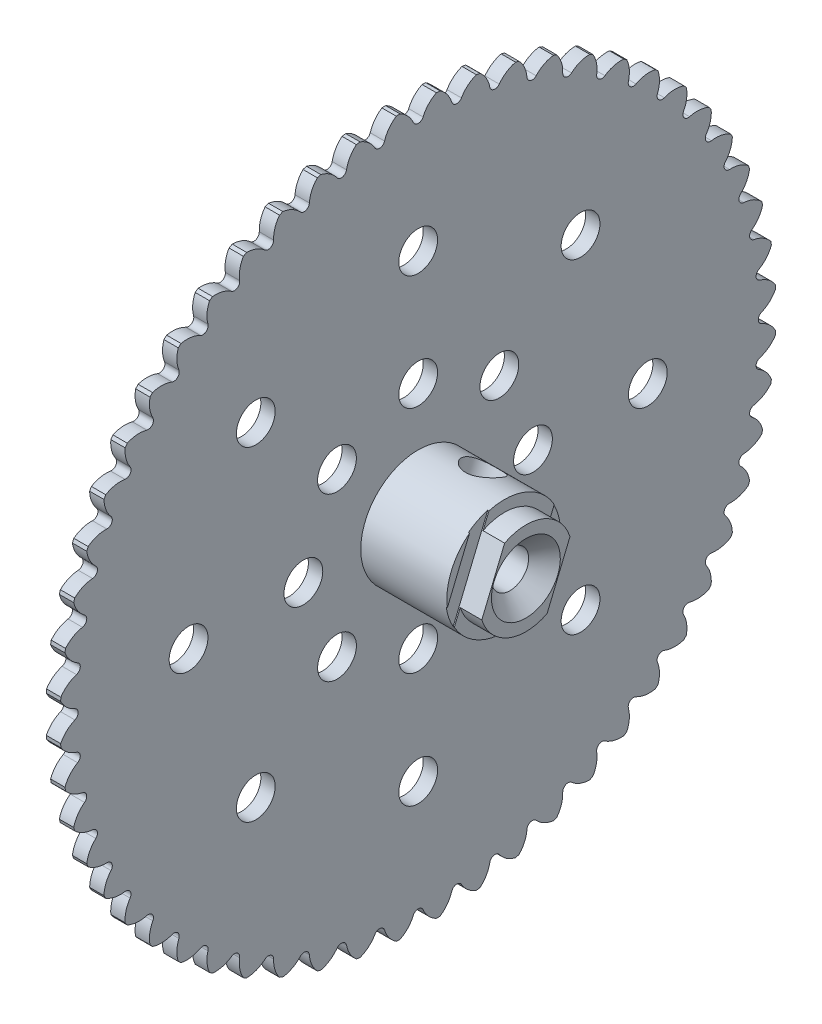
SolidWorks part; units mm, degrees
ref_plane "Front Plane" through (0, 0, 0) normal (0, 0, 1) x (1, 0, 0)
ref_plane "Top Plane" through (0, 0, 0) normal (0, 1, 0) x (1, 0, 0)
ref_plane "Right Plane" through (0, 0, 0) normal (1, 0, 0) x (0, 0, -1)
sketch "Sketch1" plane through (0, 0, 0) normal (1, 0, 0) x (0, 0, -1)
  circle A0 centre (0, 0) radius 39.5986
  dimension "D1" = 79.1972
extrude "Boss-Extrude1" add sketch "Sketch1" along normal blind 1.5875
sketch "Sketch2" plane through (1.5875, 0, 0) normal (1, 0, 0) x (0, 0, -1)
  circle A0 centre (0, 0) radius 12.7 construction
  circle A1 centre (0, 12.7) radius 2.1463
  circle A2 centre (0, 25.4) radius 2.1463
  circle A3 centre (0, 0) radius 25.4 construction
  dimension "D1" = 25.4
  dimension "D2" = 4.2926
  dimension "D3" = 50.8
extrude "Cut-Extrude1" cut sketch "Sketch2" against normal blind 1.5875
pattern_circular "CirPattern1" count 8 over 360 about axis through (1.5875, 0, 0) along (1, 0, 0) of "Cut-Extrude1"
sketch "Sketch4" plane through (1.5875, 0, 0) normal (1, 0, 0) x (0, 0, -1)
  line L0 (0, 37.6174) -> (0, 39.5986) construction
  line L1 (0, 0.8731) -> (0, -0.8731) construction
  line L2 (0, 0) -> (-2.0174, 39.5472) construction
  line L3 (0, 0) -> (2.4232, 39.5244) construction
  arc A0 (-2.0174, 39.5472) -> (-0.5366, 37.9706) centre (-3.4529, 36.7152) cw
  circle A1 centre (0, 0) radius 39.5986 construction
  arc A2 (-0.5366, 37.9706) -> (0.5366, 37.9706) centre (0, 38.2016) ccw
  arc A3 (0.5366, 37.9706) -> (2.0174, 39.5472) centre (3.4529, 36.7152) cw
  arc A4 (-2.0174, 39.5472) -> (2.4232, 39.5244) centre (0, 0) cw
  circle M13 centre (0, 0) radius 39.5986
  dimension "D1" = 0.5842
  dimension "D2" = 3.175
  dimension "D3" = 1.9812
  dimension "D4" = 6.429
  dimension "D5" = 0.4064
extrude "Cut-Extrude2" cut sketch "Sketch4" against normal blind 1.5875 contours A2 A3 A0 M13 region at (1.5875, 38.8724, 0)
pattern_circular "CirPattern2" count 56 over 360 about axis through (1.5875, 0, 0) along (1, 0, 0) of "Cut-Extrude2"
sketch "Sketch7" plane through (1.5875, 0, 0) normal (1, 0, 0) x (0, 0, -1)
  circle A0 centre (0, 0) radius 6.35
  dimension "D1" = 12.7
extrude "Boss-Extrude3" add sketch "Sketch7" along normal blind 9.525
sketch "Sketch8" plane through (11.1125, 0, 0) normal (1, 0, 0) x (0, 0, -1)
  line L0 (-4.877, -1.5525) -> (-2.3507, 4.5463)
  line L1 (2.3507, -4.5463) -> (4.877, 1.5525)
  line L3 (0, 5.1181) -> (0, -5.1181) construction
  arc A0 (-4.877, -1.5525) -> (2.3507, -4.5463) centre (0, 0) ccw
  arc A1 (4.877, 1.5525) -> (-2.3507, 4.5463) centre (0, 0) ccw
  dimension "D3" = 10.2362
  dimension "D1" = 22.5
  dimension "D2" = 7.8232
extrude "Boss-Extrude4" add sketch "Sketch8" along normal blind 2.3876
sketch "Sketch9" plane through (13.5001, 0, 0) normal (1, 0, 0) x (0, 0, -1)
  circle A0 centre (0, 0) radius 2.0574
  dimension "D1" = 4.1148
extrude "Cut-Extrude3" cut sketch "Sketch9" against normal through all contours A0
sketch "Sketch10" plane through (11.1125, 0, 0) normal (1, 0, 0) x (0, 0, -1)
  line L0 (-5.5281, -3.1245) -> (-1.6996, 6.1183)
  line L1 (-2.3507, 4.5463) -> (-4.877, -1.5525) construction
  line L2 (-6.2923, -0.8542) -> (-3.8453, 5.0534)
  line L3 (-3.9537, -9.545) -> (3.9537, 9.545) construction
  line L4 (3.8453, -5.0534) -> (6.2923, 0.8542)
  line L5 (1.6996, -6.1183) -> (5.5281, 3.1245)
  circle A0 centre (0, 0) radius 6.35 construction
  circle A1 centre (0, 0) radius 6.35 construction
  arc A4 (-1.6996, 6.1183) -> (-3.8453, 5.0534) centre (0, 0) ccw
  arc A5 (-5.5281, -3.1245) -> (-6.2923, -0.8542) centre (0, 0) cw
  arc A6 (1.6996, -6.1183) -> (3.8453, -5.0534) centre (0, 0) ccw
  arc A7 (5.5281, 3.1245) -> (6.2923, 0.8542) centre (0, 0) cw
  point P17 (0, 0)
  dimension "D1" = 1.5748
extrude "Cut-Extrude4" cut sketch "Sketch10" against normal blind 0.127
sketch "Sketch11" plane through (0, 0, 0) normal (0, 0, 1) x (1, 0, 0)
  line L3 (13.5001, -3.81) -> (13.5001, 3.81)
  line L5 (13.5001, 4.5463) -> (13.5001, -1.5525) construction
  line L6 (13.5001, 3.81) -> (9.6901, 0)
  line L7 (9.6901, 0) -> (13.5001, -3.81)
  line L8 (13.5001, 0) -> (9.6901, 0) construction
  point P3 (13.5001, 0)
  dimension "D1" = 90
  dimension "D2" = 7.62
revolve "Cut-Revolve4" cut sketch "Sketch11" angle 360 about L8 region at (12.2301, 1.27, 0)
ref_plane "Plane1" through (0, 0, 0) normal (0, -0.3827, -0.9239) x (-1, 0, 0)
sketch "Sketch12" plane through (0, 0, 0) normal (0, -0.3827, -0.9239) x (-1, 0, 0)
  line L0 (-6.35, -6.35) -> (-6.35, 6.35)
  line L1 (-1.5875, 6.35) -> (-11.1125, 6.35) construction
  line L2 (-8.3344, -6.35) -> (-8.3344, 6.35)
  line L3 (-11.1125, -6.35) -> (-1.5875, -6.35) construction
  line L4 (-8.3344, 6.35) -> (-6.35, 6.35)
  line L5 (-8.3344, -6.35) -> (-6.35, -6.35)
  point P5 (-6.35, 0)
  dimension "D1" = 4.7625
  dimension "D2" = 1.9844
revolve "Cut-Revolve5" cut sketch "Sketch12" angle 360 about L0
